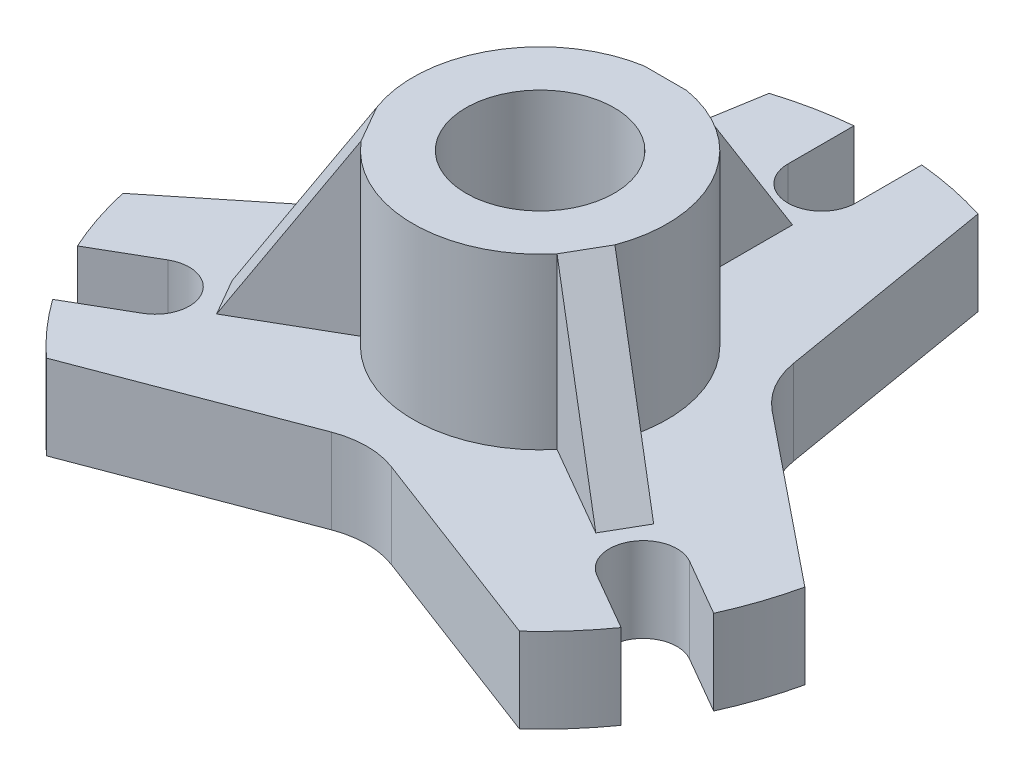
SolidWorks part; units mm, degrees
ref_plane "Front Plane" through (0, 0, 0) normal (0, 0, 1) x (1, 0, 0)
ref_plane "Top Plane" through (0, 0, 0) normal (0, 1, 0) x (1, 0, 0)
ref_plane "Right Plane" through (0, 0, 0) normal (1, 0, 0) x (0, 0, -1)
sketch "Sketch1" plane through (0, 0, 0) normal (0, 1, 0) x (1, 0, 0)
  circle A0 centre (0, 0) radius 17.5
  circle A1 centre (0, 0) radius 82.5
  circle A2 centre (0, 0) radius 30
  dimension "D1" = 35
  dimension "D2" = 60
  dimension "D3" = 165
extrude "Boss-Extrude2" add sketch "Sketch1" along normal blind 20 contours A1 A2 region at (-80.1665, 0, 0)
extrude "Boss-Extrude3" add sketch "Sketch1<4>" along normal blind 60 contours A2 A0 region at (-29.1515, 0, 0)
sketch "Sketch1<4>" plane through (0, 0, 0) normal (0, 1, 0) x (1, 0, 0) same geometry as "Sketch1"
sketch "Sketch3" plane through (0, 0, 0) normal (1, 0, 0) x (0, 0, -1)
  line L0 (17.5, 60) -> (17.5, 20)
  line L1 (82.5, 20) -> (-82.5, 20) construction
  line L2 (17.5, 20) -> (67.5, 20)
  line L3 (67.5, 20) -> (67.5, 60)
  line L4 (67.5, 60) -> (17.5, 60)
  line L5 (17.5, 20) -> (82.5, 20) construction
  dimension "D1" = 50
  dimension "D2" = 50
extrude "Boss-Extrude4" add sketch "Sketch3" along normal mid plane 10
pattern_circular "CirPattern1" count 3 over 360 about axis through (0, 60, 0) along (0, 1, 0) of "Boss-Extrude4"
sketch "Sketch14" plane through (5, 0, 0) normal (1, 0, 0) x (0, 0, -1)
  line L0 (29.5804, 60) -> (29.5804, 20)
  line L1 (29.5804, 20) -> (54.5804, 20)
  line L2 (29.5804, 20) -> (67.5, 20) construction
  line L3 (54.5804, 20) -> (29.5804, 60)
  line L4 (29.5804, 60) -> (67.5, 60)
  line L5 (67.5, 60) -> (67.5, 20)
  line L6 (67.5, 20) -> (54.5804, 20)
  dimension "D1" = 25
sketch "Sketch15" plane through (5, 0, 0) normal (1, 0, 0) x (0, 0, -1)
  line L0 (29.5804, 60) -> (54.5804, 20)
  line L1 (54.5804, 20) -> (67.5, 20)
  line L2 (67.5, 20) -> (67.5, 60)
  line L3 (67.5, 60) -> (29.5804, 60)
extrude "Cut-Extrude5" cut sketch "Sketch15" against normal blind 10
pattern_circular "CirPattern4" count 3 over 360 about axis through (0, 60, 0) along (0, 1, 0) of "Cut-Extrude5"
sketch "Sketch22" plane through (0, 20, 0) normal (0, 1, 0) x (1, 0, 0)
  line L0 (8, 66.5) -> (8, 82.1112)
  line L1 (-8, 66.5) -> (-8, 82.1112)
  line L4 (-5, 29.5804) -> (5, 29.5804) construction
  line L5 (0, 29.5804) -> (0, 82.5) construction
  line L7 (25, 16.5831) -> (25, 78.6209)
  line L8 (-25, 78.6209) -> (-25, 16.5831)
  arc A0 (-8, 66.5) -> (8, 66.5) centre (0, 66.5) ccw
  circle A1 centre (0, 0) radius 82.5 construction
  arc A2 (-8, 82.1112) -> (8, 82.1112) centre (0, 0) cw
  arc A3 (28.1174, -10.4601) -> (5, 29.5804) centre (0, 0) ccw construction
  arc A4 (-5, 29.5804) -> (-28.1174, -10.4601) centre (0, 0) ccw construction
  arc A5 (-25, 78.6209) -> (25, 78.6209) centre (0, 0) cw
  circle M18 centre (0, 0) radius 82.5
  dimension "D1" = 16
  dimension "D3" = 25
  dimension "D5" = 25
  dimension "D8" = 8
  dimension "D10" = 16
  dimension "D11" = 25
  dimension "D12" = 25
sketch "Sketch25" plane through (0, 20, 0) normal (0, 1, 0) x (1, 0, 0)
  line L0 (26.8919, 77.9941) -> (19.0724, 23.1569)
  circle A0 centre (0, 0) radius 82.5 construction
  arc A1 (28.1174, -10.4601) -> (5, 29.5804) centre (0, 0) ccw construction
  dimension "D1" = 25
extrude "Cut-Extrude7" cut sketch "Sketch22" against normal through all contours A0 L5 A5 L1 | L5 A0 L0 M18 region at (3.8168, 20, -71.222) region at (-3.8168, 20, -71.222)
pattern_circular "CirPattern5" count 3 over 360 about axis through (0, 60, 0) along (0, 1, 0) of "Cut-Extrude7"
sketch "Sketch29" plane through (0, 20, 0) normal (0, 1, 0) x (1, 0, 0)
  line L7 (-80.5105, -18.0087) -> (-34.6812, 18.9598)
  line L9 (-34.6812, 18.9598) -> (-24.6598, 78.7283)
  line L14 (24.6598, 78.7283) -> (34.6812, 18.9598)
  line L15 (34.6812, 18.9598) -> (80.5105, -18.0087)
  line L16 (-55.8507, -60.7203) -> (0, -39.5255)
  line L17 (0, -39.5255) -> (55.8507, -60.7203)
  arc A0 (-8, 82.1112) -> (-75.1104, -34.1274) centre (0, 0) ccw construction
  arc A1 (-24.6598, 78.7283) -> (-80.5105, -18.0087) centre (0, 0) ccw
  arc A2 (75.1104, -34.1274) -> (8, 82.1112) centre (0, 0) ccw construction
  arc A3 (80.5105, -18.0087) -> (24.6598, 78.7283) centre (0, 0) ccw
  arc A4 (-67.1104, -47.9838) -> (67.1104, -47.9838) centre (0, 0) ccw construction
  arc A7 (-55.8507, -60.7203) -> (55.8507, -60.7203) centre (0, 0) ccw
extrude "Cut-Extrude8" cut sketch "Sketch29" against normal through all
fillet "Fillet1" radius 20 3 edges at (-34.6812, 10, -18.9598) (0, 10, 39.5255) (34.6812, 10, -18.9598)
